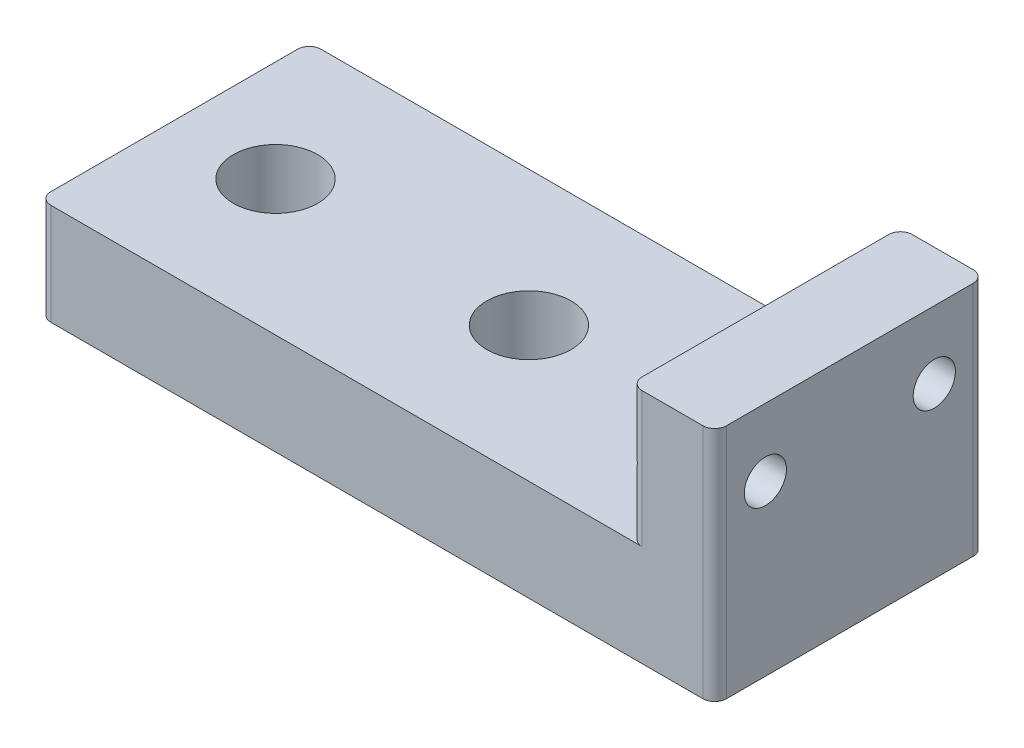
SolidWorks part; units mm, degrees
ref_plane "Front Plane" through (0, 0, 0) normal (0, 0, 1) x (1, 0, 0)
ref_plane "Top Plane" through (0, 0, 0) normal (0, 1, 0) x (1, 0, 0)
ref_plane "Right Plane" through (0, 0, 0) normal (1, 0, 0) x (0, 0, -1)
sketch "Sketch1" plane through (0, 0, 0) normal (0, 1, 0) x (1, 0, 0)
  line L1 (0, 0) -> (40, 0)
  line L2 (0, 0) -> (0, 16)
  line L3 (0, 16) -> (40, 16)
  line L4 (40, 0) -> (40, 16)
  line L9 (35, 16) -> (40, 16)
  line L10 (35, 16) -> (35, 0)
  line L11 (35, 0) -> (40, 0)
  line L12 (40, 16) -> (40, 0)
  dimension "D1" = 16
  dimension "D2" = 40
  dimension "D3" = 5
extrude "Boss-Extrude1" add sketch "Sketch1" along normal blind 6 contours L10 L3 L2 L1 | L3 L10 L1 L4 region at (17.5, 0, -8) region at (37.5, 0, -8)
extrude "Boss-Extrude2" add sketch "Sketch1<4>" along normal blind 14 contours L3 L10 L1 L4 region at (37.5, 0, -8)
sketch "Sketch1<4>" plane through (0, 0, 0) normal (0, 1, 0) x (1, 0, 0) same geometry as "Sketch1"
sketch "Sketch3" plane through (35, 0, 0) normal (-1, 0, 0) x (0, 0, 1)
  line L0 (-13, 10) -> (-3, 10) construction
  line L1 (-16, 14) -> (0, 14) construction
  line L2 (0, 6) -> (-16, 6) construction
  circle A0 centre (-13, 10) radius 1.25
  circle A1 centre (-3, 10) radius 1.25
  point P7 (-8, 14)
  point P8 (-8, 10)
  dimension "D2" = 2.5
  dimension "D1" = 10
  dimension "D3" = 4
sketch "Sketch4" plane through (0, 6, 0) normal (0, 1, 0) x (1, 0, 0)
  line L0 (0, 0) -> (0, 16) construction
  circle A0 centre (6, 8) radius 2.5
  circle A1 centre (21, 8) radius 2.5
  point P6 (0, 8)
  dimension "D2" = 5
  dimension "D1" = 6
  dimension "D3" = 15
extrude "Cut-Extrude1" cut sketch "Sketch4" against normal blind 14 contours A1 | A0 region at (21, 6, -8)
extrude "Cut-Extrude2" cut sketch "Sketch3" against normal blind 14 contours A1 | A0 region at (35, 10, -3)
fillet "Fillet1" radius 0.7 6 edges at (0, 3, -16) (0, 3, 0) (35, 10, -16) (40, 7, -16) (35, 10, 0) (40, 7, 0)
sketch "Sketch5" plane through (35, 0, 0) normal (-1, 0, 0) x (0, 0, 1)
  line L1 (-11.5566, 12.5) -> (-14.4434, 12.5)
  line L2 (-14.4434, 12.5) -> (-15.8868, 10)
  line L3 (-15.8868, 10) -> (-14.4434, 7.5)
  line L4 (-14.4434, 7.5) -> (-11.5566, 7.5)
  line L5 (-11.5566, 7.5) -> (-10.1132, 10)
  line L6 (-10.1132, 10) -> (-11.5566, 12.5)
  line L7 (-4.4434, 12.5) -> (-5.8868, 10)
  line L8 (-5.8868, 10) -> (-4.4434, 7.5)
  line L9 (-4.4434, 7.5) -> (-1.5566, 7.5)
  line L10 (-1.5566, 7.5) -> (-0.1132, 10)
  line L11 (-0.1132, 10) -> (-1.5566, 12.5)
  line L12 (-1.5566, 12.5) -> (-4.4434, 12.5)
  circle A0 centre (-13, 10) radius 2.5 construction
  circle A1 centre (-3, 10) radius 2.5 construction
  circle A2 centre (-13, 10) radius 1.25 construction
  circle A3 centre (-3, 10) radius 1.25 construction
  point P9 (0, 0)
  point P19 (0, 0)
  dimension "D1" = 5
extrude "Cut-Extrude3" cut sketch "Sketch5" against normal blind 3
